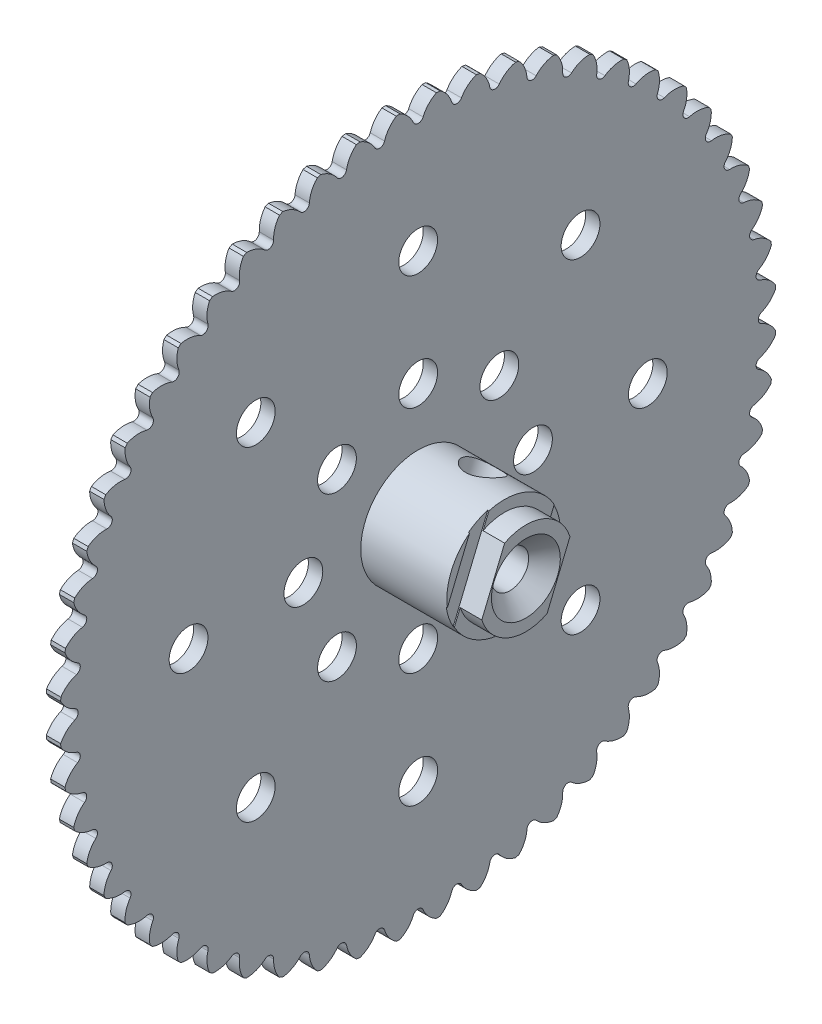
SolidWorks part; units mm, degrees
ref_plane "Front Plane" through (0, 0, 0) normal (0, 0, 1) x (1, 0, 0)
ref_plane "Top Plane" through (0, 0, 0) normal (0, 1, 0) x (1, 0, 0)
ref_plane "Right Plane" through (0, 0, 0) normal (1, 0, 0) x (0, 0, -1)
sketch "Sketch1" plane through (0, 0, 0) normal (1, 0, 0) x (0, 0, -1)
  circle A0 centre (0, 0) radius 39.5986
  dimension "D1" = 79.1972
extrude "Boss-Extrude1" add sketch "Sketch1" along normal blind 1.5875
sketch "Sketch2" plane through (1.5875, 0, 0) normal (1, 0, 0) x (0, 0, -1)
  circle A0 centre (0, 0) radius 12.7 construction
  circle A1 centre (0, 12.7) radius 2.1463
  circle A2 centre (0, 25.4) radius 2.1463
  circle A3 centre (0, 0) radius 25.4 construction
  point P7 (-1.5977, 25.3497)
  dimension "D1" = 25.4
  dimension "D2" = 4.2926
  dimension "D3" = 50.8
extrude "Cut-Extrude1" cut sketch "Sketch2" against normal blind 1.5875
pattern_circular "CirPattern1" count 8 over 360 about axis through (1.5875, 0, 0) along (1, 0, 0) of "Cut-Extrude1"
sketch "Sketch4" plane through (1.5875, 0, 0) normal (1, 0, 0) x (0, 0, -1)
  line L0 (0, 37.6174) -> (0, 39.5986) construction
  line L1 (0, 0.8731) -> (0, -0.8731) construction
  line L2 (0, 0) -> (-2.0174, 39.5472) construction
  line L3 (0, 0) -> (2.4232, 39.5244) construction
  arc A0 (-2.0174, 39.5472) -> (-0.5366, 37.9706) centre (-3.4529, 36.7152) cw
  circle A1 centre (0, 0) radius 39.5986 construction
  arc A2 (-0.5366, 37.9706) -> (0.5366, 37.9706) centre (0, 38.2016) ccw
  arc A3 (0.5366, 37.9706) -> (2.0174, 39.5472) centre (3.4529, 36.7152) cw
  arc A4 (-2.0174, 39.5472) -> (2.4232, 39.5244) centre (0, 0) cw
  point P11 (1.5114, 25.8328)
  point P16 (1.5419, 25.913)
  circle M13 centre (0, 0) radius 39.5986
  dimension "D1" = 0.5842
  dimension "D2" = 3.175
  dimension "D3" = 1.9812
  dimension "D4" = 6.429
  dimension "D5" = 0.4064
extrude "Cut-Extrude2" cut sketch "Sketch4" against normal blind 1.5875 contours A2 A3 A0 M13 region at (1.5875, 38.8724, 0)
pattern_circular "CirPattern2" count 56 over 360 about axis through (1.5875, 0, 0) along (1, 0, 0) of "Cut-Extrude2"
sketch "Sketch7" plane through (1.5875, 0, 0) normal (1, 0, 0) x (0, 0, -1)
  circle A0 centre (0, 0) radius 6.35
  dimension "D1" = 12.7
extrude "Boss-Extrude3" add sketch "Sketch7" along normal blind 9.525
sketch "Sketch8" plane through (11.1125, 0, 0) normal (1, 0, 0) x (0, 0, -1)
  line L0 (-4.877, -1.5525) -> (-2.3507, 4.5463)
  line L1 (2.3507, -4.5463) -> (4.877, 1.5525)
  line L3 (0, 5.1181) -> (0, -5.1181) construction
  arc A0 (-4.877, -1.5525) -> (2.3507, -4.5463) centre (0, 0) ccw
  arc A1 (4.877, 1.5525) -> (-2.3507, 4.5463) centre (0, 0) ccw
  dimension "D3" = 10.2362
  dimension "D1" = 22.5
  dimension "D2" = 7.8232
extrude "Boss-Extrude4" add sketch "Sketch8" along normal blind 2.3876
sketch "Sketch9" plane through (13.5001, 0, 0) normal (1, 0, 0) x (0, 0, -1)
  circle A0 centre (0, 0) radius 2.0574
  dimension "D1" = 4.1148
extrude "Cut-Extrude3" cut sketch "Sketch9" against normal through all contours A0
sketch "Sketch10" plane through (11.1125, 0, 0) normal (1, 0, 0) x (0, 0, -1)
  line L0 (-5.5281, -3.1245) -> (-1.6996, 6.1183)
  line L1 (-2.3507, 4.5463) -> (-4.877, -1.5525) construction
  line L2 (-6.2923, -0.8542) -> (-3.8453, 5.0534)
  line L3 (-3.9537, -9.545) -> (3.9537, 9.545) construction
  line L4 (3.8453, -5.0534) -> (6.2923, 0.8542)
  line L5 (1.6996, -6.1183) -> (5.5281, 3.1245)
  circle A0 centre (0, 0) radius 6.35 construction
  circle A1 centre (0, 0) radius 6.35 construction
  arc A4 (-1.6996, 6.1183) -> (-3.8453, 5.0534) centre (0, 0) ccw
  arc A5 (-5.5281, -3.1245) -> (-6.2923, -0.8542) centre (0, 0) cw
  arc A6 (1.6996, -6.1183) -> (3.8453, -5.0534) centre (0, 0) ccw
  arc A7 (5.5281, 3.1245) -> (6.2923, 0.8542) centre (0, 0) cw
  point P17 (0, 0)
  dimension "D1" = 1.5748
extrude "Cut-Extrude4" cut sketch "Sketch10" against normal blind 0.127
sketch "Sketch11" plane through (0, 0, 0) normal (0, 0, 1) x (1, 0, 0)
  line L3 (13.5001, -3.81) -> (13.5001, 3.81)
  line L5 (13.5001, 4.5463) -> (13.5001, -1.5525) construction
  line L6 (13.5001, 3.81) -> (9.6901, 0)
  line L7 (9.6901, 0) -> (13.5001, -3.81)
  line L8 (13.5001, 0) -> (9.6901, 0) construction
  point P3 (13.5001, 0)
  dimension "D1" = 90
  dimension "D2" = 7.62
revolve "Cut-Revolve4" cut sketch "Sketch11" angle 360 about L8 region at (12.2301, 1.27, 0)
ref_plane "Plane1" through (0, 0, 0) normal (0, -0.3827, -0.9239) x (-1, 0, 0)
sketch "Sketch12" plane through (0, 0, 0) normal (0, -0.3827, -0.9239) x (-1, 0, 0)
  line L0 (-6.35, -6.35) -> (-6.35, 6.35)
  line L1 (-1.5875, 6.35) -> (-11.1125, 6.35) construction
  line L2 (-8.3344, -6.35) -> (-8.3344, 6.35)
  line L3 (-11.1125, -6.35) -> (-1.5875, -6.35) construction
  line L4 (-8.3344, 6.35) -> (-6.35, 6.35)
  line L5 (-8.3344, -6.35) -> (-6.35, -6.35)
  point P5 (-6.35, 0)
  dimension "D1" = 4.7625
  dimension "D2" = 1.9844
revolve "Cut-Revolve5" cut sketch "Sketch12" angle 360 about L0
